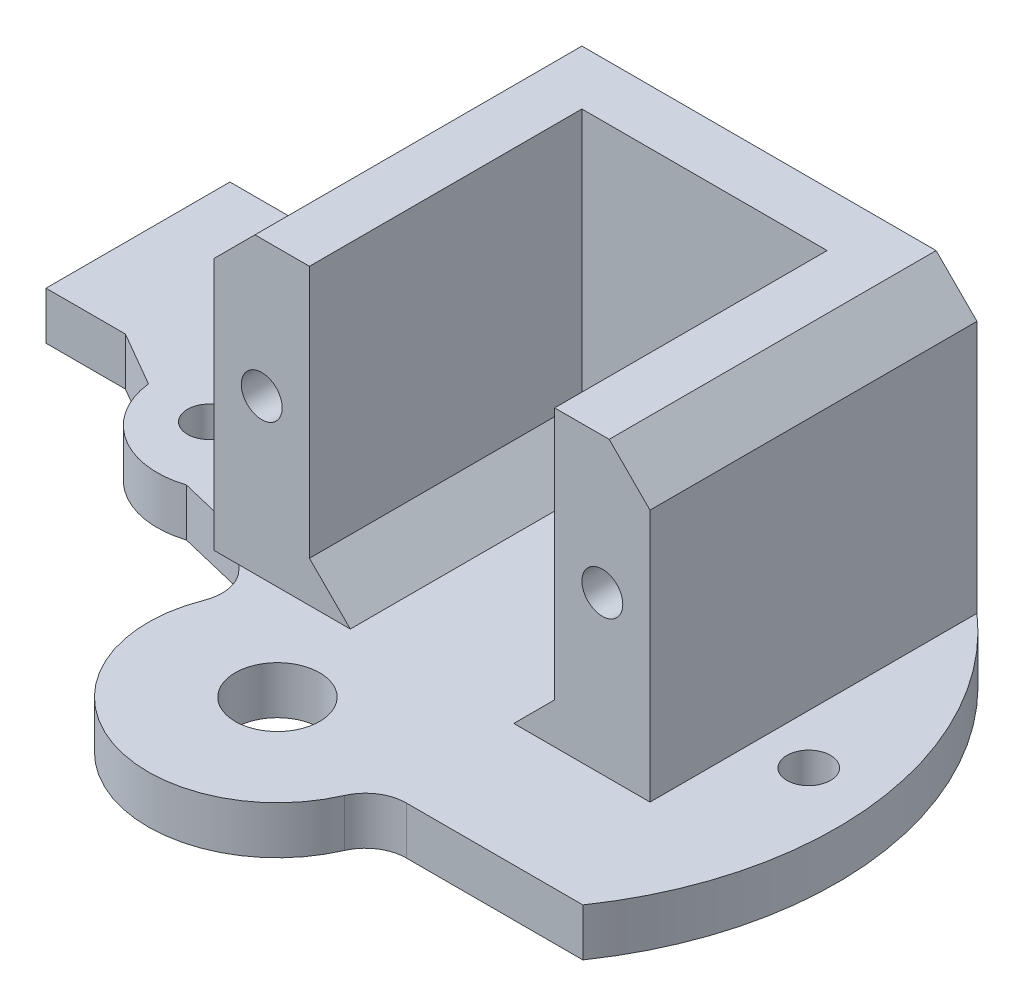
SolidWorks part; units mm, degrees
ref_plane "Alzado" through (0, 0, 0) normal (0, 0, 1) x (1, 0, 0)
ref_plane "Planta" through (0, 0, 0) normal (0, 1, 0) x (1, 0, 0)
ref_plane "Vista lateral" through (0, 0, 0) normal (1, 0, 0) x (0, 0, -1)
sketch "Croquis1" plane through (0, 0, 0) normal (0, 1, 0) x (1, 0, 0)
  line L0 (-35, 32.5) -> (35, -32.5) construction
  line L1 (-35, 32.5) -> (35, 32.5)
  line L2 (-35, 32.5) -> (-35, -32.5)
  line L3 (-35, -32.5) -> (35, -32.5)
  line L4 (35, 32.5) -> (35, -32.5)
  dimension "D1" = 70
  dimension "D2" = 65
extrude "Extruir1" add sketch "Croquis1" along normal blind 3.5
sketch "Croquis2" plane through (0, 3.5, 0) normal (0, 1, 0) x (1, 0, 0)
  line L0 (0, 32.5) -> (0, -32.5) construction
  line L1 (35, 32.5) -> (-35, 32.5) construction
  line L2 (-35, -32.5) -> (35, -32.5) construction
  circle A0 centre (0, -17.5) radius 3.1
  dimension "D1" = 6.2
  dimension "D2" = 15
extrude "Extruir2" cut sketch "Croquis2" against normal blind 5
sketch "Croquis3" plane through (0, 3.5, 0) normal (0, 1, 0) x (1, 0, 0)
  line L0 (0, -32.5) -> (0, 32.5) construction
  line L1 (-35, -32.5) -> (35, -32.5) construction
  line L2 (35, 32.5) -> (-35, 32.5) construction
  line L3 (-32.9868, -32.5) -> (-32.9868, 32.5) construction
  line L4 (-32.9868, 1.5) -> (-12.9615, 1.5)
  line L5 (18.8496, -32.5) -> (18.8496, 32.5) construction
  line L6 (-32.9868, 3.5) -> (18.8496, 3.5) construction
  line L7 (-32.9868, 2) -> (0, 2) construction
  line L8 (-32.9868, 11.5) -> (18.8496, 11.5) construction
  line L9 (0, -17.5) -> (-14.8492, -2.6508) construction
  line L10 (0, -17.5) -> (14.8492, -2.6508) construction
  line L11 (0, 2) -> (18.8496, 2) construction
  line L12 (-32.9868, 2) -> (18.8496, 2) construction
  line L13 (-32.9868, 12) -> (18.8496, 12)
  line L14 (-5.3033, -12.1967) -> (-16.2635, -1.2365) construction
  line L15 (12.9615, 1.5) -> (18.8496, 1.5)
  line L16 (-32.9868, 1.5) -> (18.8496, 1.5) construction
  line L17 (7.9844, -18) -> (22.9946, -18)
  line L18 (-5.9993, -12.2078) -> (-16.6132, -1.5939)
  line L19 (0, -17.5) -> (23, -17.5) construction
  line L20 (7.5, -17.5) -> (23, -17.5) construction
  line L21 (-5.6569, -12.5503) -> (-16.617, -1.5901) construction
  line L22 (7.5, -18) -> (23, -18) construction
  line L23 (-32.9868, 12) -> (-32.9868, 1.5)
  line L24 (18.8496, 12) -> (18.8496, 1.5)
  line L25 (-34.4868, 13.5) -> (20.3496, 13.5)
  line L26 (20.3496, 13.5) -> (20.3496, 0)
  line L27 (17.1464, 0) -> (20.3496, 0)
  line L28 (9.2871, -19.5) -> (24.4182, -19.5)
  line L29 (-7.9812, -12.3473) -> (-18.6805, -1.6479)
  line L30 (-34.4868, 0) -> (-17.1464, 0)
  line L31 (-34.4868, 13.5) -> (-34.4868, 0)
  circle A0 centre (0, -17.5) radius 21 construction
  circle A1 centre (0, -17.5) radius 7.5 construction
  arc A2 (-12.9615, 1.5) -> (-16.6132, -1.5939) centre (0, -17.5) ccw
  circle A3 centre (0, -17.5) radius 23 construction
  arc A4 (-5.9993, -12.2078) -> (7.9844, -18) centre (0, -17.5) ccw
  arc A5 (22.9946, -18) -> (12.9615, 1.5) centre (0, -17.5) ccw
  arc A6 (24.4182, -19.5) -> (17.1464, 0) centre (0, -17.5) ccw
  arc A7 (-7.9812, -12.3473) -> (9.2871, -19.5) centre (0, -17.5) ccw
  arc A8 (-17.1464, 0) -> (-18.6805, -1.6479) centre (0, -17.5) ccw
  dimension "D3" = 42
  dimension "D8" = 15
  dimension "D9" = 46
  dimension "D14" = 0.5
  dimension "D2" = 51.8364
  dimension "D6" = 90
  dimension "D7" = 45
  dimension "D1" = 32.9868
  dimension "D4" = 1.5
  dimension "D5" = 9.5
  dimension "D10" = 2
  dimension "D11" = 0.5
  dimension "D12" = 0.5
  dimension "D13" = 0.5
  dimension "D15" = 1.5
extrude "Extruir3" add sketch "Croquis3" along normal blind 10
sketch "Croquis4" plane through (0, 3.5, 0) normal (0, 1, 0) x (1, 0, 0)
  line L0 (-34.4868, 0) -> (-17.1464, 0) construction
  line L1 (-34.4868, 13.5) -> (-34.4868, 0) construction
  line L2 (20.3496, 13.5) -> (-34.4868, 13.5) construction
  line L3 (20.3496, 0) -> (20.3496, 13.5) construction
  line L4 (17.1464, 0) -> (20.3496, 0) construction
  line L5 (9.2871, -19.5) -> (24.4182, -19.5) construction
  line L6 (-18.6805, -1.6479) -> (-7.9812, -12.3473) construction
  line L7 (-34.4868, 0) -> (-17.1464, 0)
  line L8 (-34.4868, 13.5) -> (-34.4868, 0)
  line L9 (20.3496, 13.5) -> (-34.4868, 13.5)
  line L10 (20.3496, 0) -> (20.3496, 13.5)
  line L11 (17.1464, 0) -> (20.3496, 0)
  line L12 (9.2871, -19.5) -> (24.4182, -19.5)
  line L13 (-18.6805, -1.6479) -> (-7.9812, -12.3473)
  arc A0 (-17.1464, 0) -> (-18.6805, -1.6479) centre (0, -17.5) ccw construction
  arc A1 (24.4182, -19.5) -> (17.1464, 0) centre (0, -17.5) ccw construction
  arc A2 (-7.9812, -12.3473) -> (9.2871, -19.5) centre (0, -17.5) ccw construction
  arc A3 (-17.1464, 0) -> (-18.6805, -1.6479) centre (0, -17.5) ccw
  arc A4 (24.4182, -19.5) -> (17.1464, 0) centre (0, -17.5) ccw
  arc A5 (-7.9812, -12.3473) -> (9.2871, -19.5) centre (0, -17.5) ccw
extrude "Extruir4" cut sketch "Croquis4" against normal blind 10 flip side to cut
fillet "Redondeo1" radius 3 4 edges at (9.2871, 6.75, 19.5) (-7.9812, 6.75, 12.3473) (7.9844, 8.5, 18) (-5.9993, 8.5, 12.2078)
sketch "Croquis5" plane through (0, 0, 0) normal (0, -1, 0) x (1, 0, 0)
  line L0 (-18.6805, 1.6479) -> (-9.5151, 10.8133) construction
  line L1 (-34.4868, 0) -> (-17.1464, 0) construction
  line L2 (-18.6805, 1.6479) -> (-14.4379, 5.8906)
  line L3 (-24.4498, 0) -> (-17.1464, 0)
  line L4 (20.3496, 0) -> (20.3496, -13.5) construction
  line L5 (17.1464, 0) -> (20.3496, 0) construction
  line L6 (20.3496, 0) -> (20.3496, -13.5)
  line L7 (17.1464, 0) -> (20.3496, 0)
  arc A0 (-14.4379, 5.8906) -> (-24.4498, 0) centre (-18.6805, 1.6479) ccw
  arc A1 (-18.6805, 1.6479) -> (-17.1464, 0) centre (0, 17.5) ccw construction
  arc A2 (-18.6805, 1.6479) -> (-17.1464, 0) centre (0, 17.5) ccw
  arc A3 (24.4182, 19.5) -> (20.3496, -13.5) centre (3.8531, 5.2847) cw
  arc A4 (17.1464, 0) -> (24.4182, 19.5) centre (0, 17.5) ccw construction
  arc A5 (17.1464, 0) -> (24.4182, 19.5) centre (0, 17.5) ccw
  dimension "D1" = 12
  dimension "D2" = 25
extrude "Extruir5" add sketch "Croquis5" against normal up to surface (13.5 mm away) up to face at (-1.8278, 13.5, 5.5887)
chamfer "Chaflán1" distance 5 angle 45 2 edges at (-14.4379, 6.75, 5.8906) (-24.4498, 6.75, 0) first distance on face at (-11.9765, 6.75, 8.3519) first distance on face at (-29.4683, 6.75, 0)
sketch "Croquis6" plane through (0, 13.5, 0) normal (0, 1, 0) x (1, 0, 0)
  line L7 (-34.4868, 13.5) -> (-34.4868, 0)
  line L8 (-34.4868, 0) -> (-28.6614, 0)
  line L9 (-28.6614, 0) -> (-24.6424, -2.3231)
  line L10 (-16.83, -7.3554) -> (-11.7523, -8.5761)
  line L11 (-11.7523, -8.5761) -> (-9.5151, -10.8133)
  line L12 (11.4564, -19.5) -> (24.4182, -19.5)
  line L13 (20.3496, 13.5) -> (-34.4868, 13.5)
  line L14 (-34.4868, 13.5) -> (-34.4868, 0)
  line L15 (-34.4868, 0) -> (-28.6614, 0)
  line L16 (-28.6614, 0) -> (-24.6424, -2.3231)
  line L17 (-16.83, -7.3554) -> (-11.7523, -8.5761)
  line L18 (-11.7523, -8.5761) -> (-9.5151, -10.8133)
  line L19 (11.4564, -19.5) -> (24.4182, -19.5)
  line L20 (20.3496, 13.5) -> (-34.4868, 13.5)
  arc A5 (-24.6424, -2.3231) -> (-16.83, -7.3554) centre (-18.6805, -1.6479) ccw
  arc A6 (-8.8437, -14.0303) -> (-9.5151, -10.8133) centre (-11.6365, -12.9346) ccw
  arc A7 (-8.8437, -14.0303) -> (8.7069, -21.3) centre (0, -17.5) ccw
  arc A8 (11.4564, -19.5) -> (8.7069, -21.3) centre (11.4564, -22.5) ccw
  arc A9 (24.4182, -19.5) -> (20.3496, 13.5) centre (3.8531, -5.2847) ccw
  arc A10 (-24.6424, -2.3231) -> (-16.83, -7.3554) centre (-18.6805, -1.6479) ccw
  arc A11 (-8.8437, -14.0303) -> (-9.5151, -10.8133) centre (-11.6365, -12.9346) ccw
  arc A12 (-8.8437, -14.0303) -> (8.7069, -21.3) centre (0, -17.5) ccw
  arc A13 (11.4564, -19.5) -> (8.7069, -21.3) centre (11.4564, -22.5) ccw
  arc A14 (24.4182, -19.5) -> (20.3496, 13.5) centre (3.8531, -5.2847) ccw
  dimension "D1" = 0
extrude "Extruir6" add sketch "Croquis6" along normal blind 3.5 separate body
sketch "Croquis7" plane through (0, 17, 0) normal (0, 1, 0) x (1, 0, 0)
  line L0 (20.3496, 13.5) -> (-34.4868, 13.5) construction
  circle A0 centre (-20, -2.5) radius 1.6
  circle A1 centre (24, -2.5) radius 1.6
  dimension "D1" = 3.2
  dimension "D2" = 16
  dimension "D3" = 20
  dimension "D4" = 24
extrude "Extruir7" cut sketch "Croquis7" against normal through all
sketch "Croquis8" plane through (0, 17, 0) normal (0, 1, 0) x (1, 0, 0)
  circle A0 centre (0, -17.5) radius 3.1 construction
  circle A1 centre (0, -17.5) radius 3.1
extrude "Extruir8" cut sketch "Croquis8" against normal blind 5
sketch "Croquis9" plane through (0, 13.5, 0) normal (0, 1, 0) x (1, 0, 0)
  line L0 (18.8496, 1.5) -> (18.8496, 12) construction
  line L1 (18.8496, 1.5) -> (18.8496, 12)
  line L2 (19.5496, 1.5) -> (19.5496, 12)
  line L3 (18.8496, 12) -> (19.5496, 12)
  line L4 (18.8496, 1.5) -> (19.5496, 1.5)
  dimension "D1" = 0.7
extrude "Extruir9" cut sketch "Croquis9" against normal up to surface (10 mm away) up to face at (-1.6185, 3.5, 4.8365)
sketch "Croquis10" plane through (19.5496, 0, 0) normal (-1, 0, 0) x (0, 0, 1)
  line L0 (-5.875, 13.5) -> (-5.875, 3.5) construction
  line L3 (-1.5, 13.5) -> (-12, 13.5) construction
  line L4 (-12, 3.5) -> (-12, 13.5) construction
  line L5 (-5.875, 13.5) -> (-12, 3.5) construction
  line L6 (-12, 3.5) -> (-1.5, 3.5) construction
  line L7 (-8.9375, 8.5) -> (-12, 13.5) construction
  line L8 (19.5, 13.5) -> (-13.5, 13.5) construction
  line L10 (-7.4062, 11) -> (-10.4687, 11)
  line L11 (-7.4062, 11) -> (-7.4062, 6)
  line L12 (-7.4062, 6) -> (-10.4687, 6)
  line L13 (-10.4687, 11) -> (-10.4687, 6)
  dimension "D1" = 6.125
  dimension "D2" = 5
  dimension "D3" = 3.0625
extrude "Extruir10" cut sketch "Croquis10" against normal blind 10 and the other way through all
delete or keep bodies "Sólido-Eliminar1" type delete bodies bodies 111
sketch "Croquis11" plane through (0, 0, -13.5) normal (0, 0, -1) x (-1, 0, 0)
  line L0 (34.4868, 17) -> (34.4868, 47)
  line L1 (34.4868, 47) -> (-20.3496, 47)
  line L2 (-20.3496, 47) -> (-20.3496, 17)
  line L3 (-20.3496, 17) -> (34.4868, 17)
  dimension "D1" = 30
  dimension "D2" = 30
extrude "Saliente-Extruir1" add sketch "Croquis11" against normal blind 4
sketch "Croquis13" plane through (0, 0, -9.5) normal (0, 0, 1) x (1, 0, 0)
  line L0 (-11.6504, 47) -> (-4.6504, 47)
  line L1 (-34.4868, 47) -> (20.3496, 47) construction
  line L2 (-4.6504, 47) -> (-4.6504, 17)
  line L3 (8.7069, 17) -> (-9.5, 17) construction
  line L4 (20.3496, 47) -> (13.3496, 47)
  line L5 (13.3496, 47) -> (13.3496, 17)
  line L6 (-11.6504, 47) -> (-11.6504, 17)
  line L7 (20.3496, 17) -> (-34.4868, 17) construction
  line L8 (-11.6504, 17) -> (-4.6504, 17)
  line L9 (13.3496, 17) -> (20.3496, 17)
  line L10 (20.3496, 17) -> (20.3496, 47)
  line L11 (16.8496, 17) -> (16.8496, 47) construction
  line L13 (-8.1504, 17) -> (-8.1504, 47) construction
  dimension "D1" = 7
  dimension "D2" = 7
  dimension "D3" = 25
extrude "Saliente-Extruir2" add sketch "Croquis13" along normal blind 20
sketch "Croquis14" plane through (0, 47, 0) normal (0, 1, 0) x (1, 0, 0)
  line L10 (20.3496, 13.5) -> (-34.4868, 13.5)
  line L11 (-34.4868, 13.5) -> (-34.4868, 9.5)
  line L12 (-34.4868, 9.5) -> (-11.6504, 9.5)
  line L13 (-11.6504, 9.5) -> (-11.6504, -10.5)
  line L14 (-11.6504, -10.5) -> (-4.6504, -10.5)
  line L15 (-4.6504, -10.5) -> (-4.6504, 9.5)
  line L16 (-4.6504, 9.5) -> (13.3496, 9.5)
  line L17 (13.3496, 9.5) -> (13.3496, -10.5)
  line L18 (13.3496, -10.5) -> (20.3496, -10.5)
  line L19 (20.3496, -10.5) -> (20.3496, 13.5)
  line L20 (20.3496, 13.5) -> (-34.4868, 13.5)
  line L21 (-34.4868, 13.5) -> (-34.4868, 9.5)
  line L22 (-34.4868, 9.5) -> (-11.6504, 9.5)
  line L23 (-11.6504, 9.5) -> (-11.6504, -10.5)
  line L24 (-11.6504, -10.5) -> (-4.6504, -10.5)
  line L25 (-4.6504, -10.5) -> (-4.6504, 9.5)
  line L26 (-4.6504, 9.5) -> (13.3496, 9.5)
  line L27 (13.3496, 9.5) -> (13.3496, -10.5)
  line L28 (13.3496, -10.5) -> (20.3496, -10.5)
  line L29 (20.3496, -10.5) -> (20.3496, 13.5)
  dimension "D1" = 0
extrude "Cortar-Extruir1" cut sketch "Croquis14" against normal blind 8.44
sketch "Croquis15" plane through (0, 0, -9.5) normal (0, 0, 1) x (1, 0, 0)
  line L4 (-11.6504, 38.56) -> (-34.4868, 38.56)
  line L5 (-34.4868, 38.56) -> (-34.4868, 17)
  line L6 (-34.4868, 17) -> (-11.6504, 17)
  line L7 (-11.6504, 17) -> (-11.6504, 38.56)
  line L8 (-11.6504, 38.56) -> (-34.4868, 38.56)
  line L9 (-34.4868, 38.56) -> (-34.4868, 17)
  line L10 (-34.4868, 17) -> (-11.6504, 17)
  line L11 (-11.6504, 17) -> (-11.6504, 38.56)
  dimension "D1" = 0
extrude "Cortar-Extruir2" cut sketch "Croquis15" against normal blind 8.44
chamfer "Chaflán2" distance 3 angle 45 3 edges at (13.3496, 17, 0.5) (-4.6504, 17, 0.5)
sketch "Croquis16" plane through (0, 0, 10.5) normal (0, 0, 1) x (1, 0, 0)
  line L0 (-8.1504, 17) -> (-8.1504, 47) construction
  line L1 (16.8496, 17) -> (16.8496, 47) construction
  line L2 (-11.6504, 38.56) -> (-4.6504, 38.56) construction
  circle A0 centre (-8.1504, 28.56) radius 1.5
  circle A1 centre (16.8496, 28.56) radius 1.5
  dimension "D1" = 3
  dimension "D2" = 10
extrude "Cortar-Extruir3" cut sketch "Croquis16" against normal through all
chamfer "Chaflán3" distance 3 angle 45 2 edges at (20.3496, 38.56, -1.5) (-11.6504, 38.56, -1.5)
move or copy body "Sólido-Mover/Copiar1" [suppressed] bodies to move or copy 117
